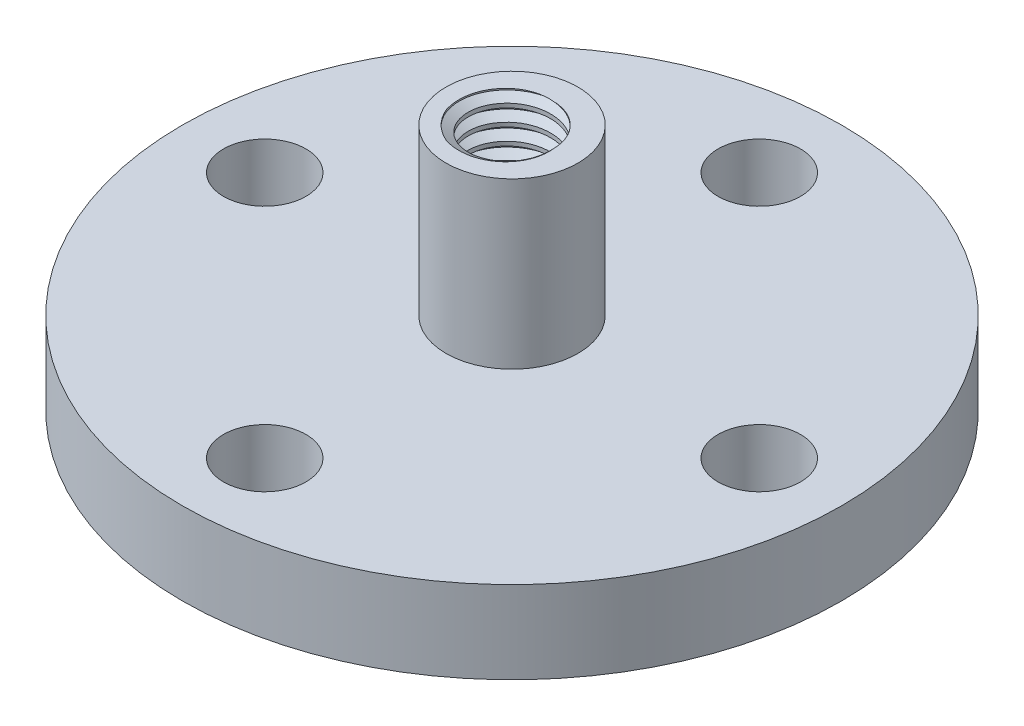
SolidWorks part; units mm, degrees
ref_plane "Спереди" through (0, 0, 0) normal (0, 0, 1) x (1, 0, 0)
ref_plane "Сверху" through (0, 0, 0) normal (0, 1, 0) x (1, 0, 0)
ref_plane "Справа" through (0, 0, 0) normal (1, 0, 0) x (0, 0, -1)
sketch "Эскиз1" plane through (0, 0, 0) normal (0, 1, 0) x (1, 0, 0)
  line L0 (0, 0) -> (15, 0) construction
  circle A0 centre (0, 0) radius 15
  circle A1 centre (15, 0) radius 2.5
  circle A2 centre (0, -15) radius 2.5
  circle A3 centre (-15, 0) radius 2.5
  circle A4 centre (0, 15) radius 2.5
  circle A5 centre (0, 0) radius 20
  point P14 (0, 0)
  dimension "D1" = 30
  dimension "D2" = 5
  dimension "D6" = 40
  dimension "D4" = 30
  dimension "D5" = 15
  dimension "D3" = 4
extrude "Бобышка-Вытянуть1" add sketch "Эскиз1" along normal blind 5 contours A5 A4 A0 A1 A2 A3 | A4 A0 A3 A2 A1 region at (0, 0, 0) region at (-19.4343, 0, 0)
sketch "Эскиз2" plane through (0, 5, 0) normal (0, 1, 0) x (1, 0, 0)
  circle A0 centre (0, 0) radius 2.5
  circle A1 centre (0, 0) radius 4
  dimension "D1" = 5
  dimension "D2" = 8
extrude "Бобышка-Вытянуть2" add sketch "Эскиз2" along normal blind 10
thread "Резьба1" pitch 1 method cut profile "Профиль резьбы1" start angle 0, offset 0, length 0, pitch 1, diameter 5
ref_plane "Плоскость4" through (2.5, 5, 0) normal (0, 0, 1) x (1, 0, 0)
sketch "Профиль резьбы1" plane through (2.5, 5, 0) normal (0, 0, 1) x (1, 0, 0)
  line L0 (0, 0) -> (0, 1) construction
  line L1 (0, 0) -> (0.5413, 0.3125)
  line L2 (0.5413, 0.3125) -> (0.5413, 0.4375)
  line L3 (0.5413, 0.4375) -> (0, 0.75)
  line L4 (0.5413, 0.375) -> (0, 0.375) construction
  line L11 (0, 0) -> (0, 0.75)
  point P2 (0, 0)
  dimension "Pitch" = 1
  dimension "Profile_Angle" = 60
  dimension "Profile_Land" = 0.125
  dimension "Profile_Height" = 0.5413
